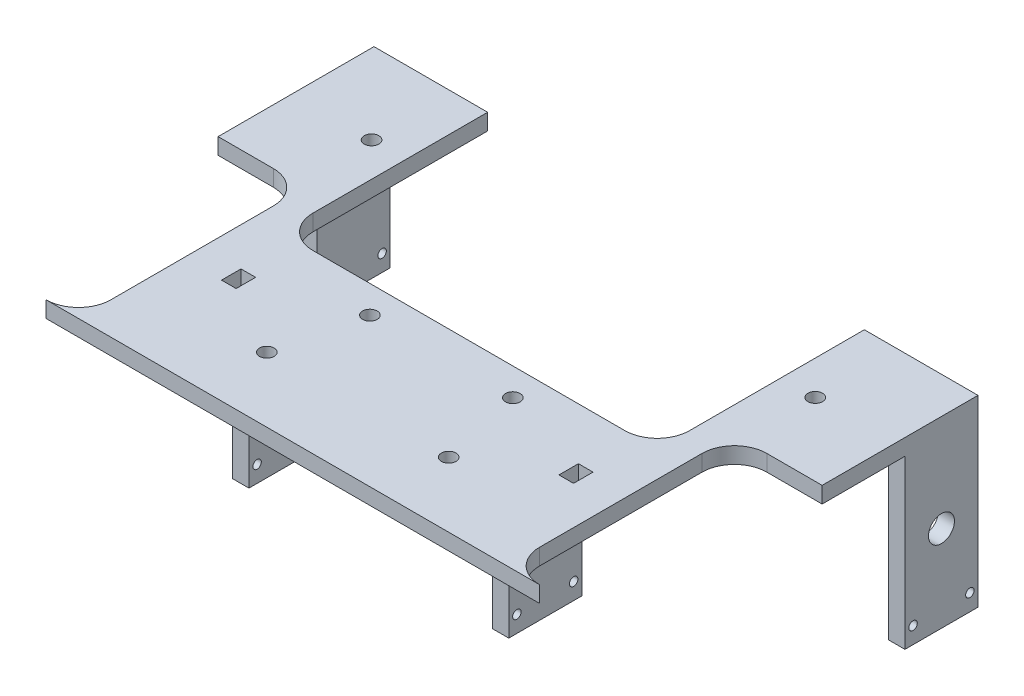
SolidWorks part; units mm, degrees
ref_plane "Front Plane" through (0, 0, 0) normal (0, 0, 1) x (1, 0, 0)
ref_plane "Top Plane" through (0, 0, 0) normal (0, 1, 0) x (1, 0, 0)
ref_plane "Right Plane" through (0, 0, 0) normal (1, 0, 0) x (0, 0, -1)
sketch "Sketch1" plane through (0, 0, 0) normal (0, 1, 0) x (1, 0, 0)
  line L0 (0, 0) -> (0, -300)
  line L1 (0, -300) -> (186, -300)
  line L2 (186, -300) -> (186, 0)
  line L3 (186, 0) -> (176, 0)
  line L4 (176, 0) -> (151, 0)
  line L5 (151, 0) -> (151, -56.1159)
  line L6 (151, -56.1159) -> (35, -56.1159)
  line L7 (35, -56.1159) -> (35, 0)
  line L8 (35, 0) -> (10, 0)
  line L9 (10, 0) -> (0, 0)
  line L10 (93, -300) -> (93, -56.1159) construction
  point P9 (93, -56.1159)
  dimension "D1" = 300
  dimension "D2" = 10
  dimension "D3" = 186
  dimension "D5" = 10
  dimension "D6" = 35
extrude "Boss-Extrude1" add sketch "Sketch1" along normal blind 5
sketch "Sketch2" plane through (0, 0, 0) normal (0, -1, 0) x (1, 0, 0)
  line L1 (50.5, 94) -> (55.5, 94)
  line L2 (50.5, 94) -> (50.5, 71.5)
  line L3 (50.5, 71.5) -> (55.5, 71.5)
  line L4 (55.5, 94) -> (55.5, 71.5)
  line L6 (135.5, 94) -> (130.5, 94)
  line L7 (135.5, 94) -> (135.5, 71.5)
  line L8 (135.5, 71.5) -> (130.5, 71.5)
  line L9 (130.5, 94) -> (130.5, 71.5)
  line L10 (0, 300) -> (186, 300) construction
  line L11 (186, 300) -> (186, 0) construction
  line L12 (0, 0) -> (0, 300) construction
  dimension "D1" = 5
  dimension "D2" = 22.5
  dimension "D3" = 5
  dimension "D4" = 206
  dimension "D5" = 22.5
  dimension "D6" = 50.5
  dimension "D7" = 50.5
extrude "Boss-Extrude2" add sketch "Sketch2" along normal blind 38
sketch "Sketch5" plane through (0, 0, 0) normal (0, -1, 0) x (1, 0, 0)
  line L0 (186, 300) -> (186, 0) construction
  line L1 (186, 295) -> (161, 295)
  line L2 (186, 295) -> (186, 300)
  line L3 (186, 300) -> (161, 300)
  line L4 (161, 295) -> (161, 300)
  line L5 (0, 300) -> (186, 300) construction
  line L6 (186, 240) -> (161, 240)
  line L7 (186, 240) -> (186, 245)
  line L8 (186, 245) -> (161, 245)
  line L9 (161, 240) -> (161, 245)
  line L10 (186, 185) -> (161, 185)
  line L11 (186, 185) -> (186, 190)
  line L12 (186, 190) -> (161, 190)
  line L13 (161, 185) -> (161, 190)
  line L14 (186, 130) -> (161, 130)
  line L15 (186, 130) -> (186, 135)
  line L16 (186, 135) -> (161, 135)
  line L17 (161, 130) -> (161, 135)
  dimension "D1" = 5
  dimension "D2" = 5
  dimension "D3" = 5
  dimension "D4" = 5
  dimension "D5" = 50
  dimension "D6" = 50
  dimension "D7" = 50
  dimension "D8" = 25
extrude "Boss-Extrude3" add sketch "Sketch5" along normal blind 30
fillet "Fillet3" radius 5 4 edges at (173.5, 0, 130) (173.5, 0, 185) (173.5, 0, 240) (173.5, 0, 295)
sketch "Sketch6" plane through (0, 0, 300) normal (0, 0, 1) x (1, 0, 0)
  line L0 (186, -30) -> (161, -30) construction
  line L1 (186, 5) -> (186, -30) construction
  circle A0 centre (178, -24) radius 3
  dimension "D1" = 6
  dimension "D2" = 6
  dimension "D3" = 8
extrude "Cut-Extrude4" cut sketch "Sketch6" against normal blind 172
sketch "Sketch7" plane through (0, 0, 0) normal (0, -1, 0) x (1, 0, 0)
  line L0 (0, 0) -> (0, 300) construction
  line L1 (0, 22.5) -> (5, 22.5)
  line L2 (0, 22.5) -> (0, 0)
  line L3 (0, 0) -> (5, 0)
  line L4 (5, 22.5) -> (5, 0)
  line L5 (186, 125) -> (186, 0) construction
  line L6 (186, 22.5) -> (181, 22.5)
  line L7 (186, 22.5) -> (186, 0)
  line L8 (186, 0) -> (181, 0)
  line L9 (181, 22.5) -> (181, 0)
  line L10 (186, 0) -> (151, 0) construction
  dimension "D1" = 5
  dimension "D2" = 5
  dimension "D3" = 22.5
  dimension "D4" = 22.5
extrude "Boss-Extrude4" add sketch "Sketch7" along normal blind 51.5
sketch "Sketch3" plane through (186, 0, 0) normal (1, 0, 0) x (0, 0, -1)
  line L4 (-71.5, 0) -> (-94, 0)
  line L5 (-71.5, -38) -> (-71.5, 0)
  line L6 (-94, -38) -> (-71.5, -38)
  line L7 (-94, 0) -> (-94, -38)
  line L9 (-71.5, -38) -> (-71.5, 0)
  line L10 (-94, -38) -> (-71.5, -38)
  line L11 (-94, 0) -> (-94, -38)
  line L13 (-71.5, 0) -> (-94, 0)
  circle A0 centre (-74, -32.9) radius 1.3 construction
  circle A1 centre (-91.5, -32.9) radius 1.3 construction
  circle A2 centre (-74, -32.9) radius 1.3
  circle A3 centre (-91.5, -32.9) radius 1.3
  circle A4 centre (-20, -46.4) radius 1.3 construction
  circle A5 centre (-2.5, -46.4) radius 1.3 construction
  circle A6 centre (-20, -46.4) radius 1.3
  circle A7 centre (-2.5, -46.4) radius 1.3
  dimension "D1" = 0
extrude "Cut-Extrude2" cut sketch "Sketch3" against normal through all contours A3 | A2 | A6 | A7
sketch "Sketch9" plane through (0, 0, 0) normal (0, -1, 0) x (1, 0, 0)
  line L0 (35, 0) -> (5, 0) construction
  line L1 (35, 0) -> (151, 0)
  line L2 (35, 0) -> (35, 63.7796)
  line L3 (35, 63.7796) -> (151, 63.7796)
  line L4 (151, 0) -> (151, 63.7796)
  line L5 (35, 56.1159) -> (35, 0) construction
  line L6 (151, 0) -> (151, 56.1159) construction
extrude "Cut-Extrude6" cut sketch "Sketch9" against normal blind 10
sketch "Sketch10" plane through (0, -30, 0) normal (0, -1, 0) x (1, 0, 0)
  line L1 (186, 295) -> (161, 295)
  line L2 (186, 295) -> (186, 300)
  line L3 (186, 300) -> (161, 300)
  line L4 (161, 295) -> (161, 300)
  line L5 (161, 130) -> (186, 130)
  line L6 (161, 130) -> (161, 135)
  line L7 (161, 135) -> (186, 135)
  line L8 (186, 130) -> (186, 135)
extrude "Boss-Extrude5" add sketch "Sketch10" along normal blind 70
sketch "Sketch11" plane through (186, 0, 0) normal (1, 0, 0) x (0, 0, -1)
  line L0 (-300, -100) -> (-304.9019, -134.6439)
  line L1 (-304.9019, -134.6439) -> (-300, -135.3374)
  line L2 (-300, -135.3374) -> (-295, -100)
  line L3 (-300, -100) -> (-295, -100)
extrude "Boss-Extrude6" add sketch "Sketch11" against normal blind 25
sketch "Sketch12" plane through (0, -100, 0) normal (0, -1, 0) x (1, 0, 0)
  line L1 (161, 130) -> (186, 130)
  line L2 (161, 130) -> (161, 135)
  line L3 (161, 135) -> (186, 135)
  line L4 (186, 130) -> (186, 135)
extrude "Boss-Extrude7" add sketch "Sketch12" along normal blind 19.72
sketch "Sketch13" plane through (0, 0, 130) normal (0, 0, -1) x (-1, 0, 0)
  line L0 (-186, -115.3141) -> (-186, -119.72)
  line L1 (-186, -119.72) -> (-186, -5) construction
  line L2 (-186, -119.72) -> (-161, -123.1352)
  line L3 (-161, -123.1352) -> (-161, -115.3141)
  line L4 (-161, -115.3141) -> (-186, -115.3141)
  line L5 (-161, -119.72) -> (-161, -5) construction
  line L8 (-88.5025, -135.5912) -> (-182.3051, -122.777) construction
extrude "Boss-Extrude8" add sketch "Sketch13" along normal blind 15 and the other way blind 4
sketch "Sketch14" plane through (19.4625, -142.4702, 0) normal (0.1354, -0.9908, 0) x (0.9908, 0.1354, 0)
  line L0 (186.3576, 115) -> (168.0843, 132.0374)
  line L1 (168.0843, 115) -> (142.8521, 115) construction
  line L2 (168.0843, 115) -> (168.0843, 134) construction
  line L3 (168.0843, 132.0374) -> (198.0152, 130.431)
  line L4 (198.0152, 130.431) -> (197.5151, 111.3666)
  line L5 (197.5151, 111.3666) -> (186.3576, 109.6075)
  line L6 (186.3576, 109.6075) -> (186.3576, 115)
extrude "Cut-Extrude7" cut sketch "Sketch14" against normal blind 15
sketch "Sketch15" plane through (0, 39.652, 280.2402) normal (0, 0.1401, 0.9901) x (1, 0, 0)
  line L1 (161, -141.043) -> (161, -176.032) construction
  line L2 (186, -141.043) -> (161, -141.043) construction
  line L3 (186, -141.043) -> (186, -176.032) construction
  line L4 (161, -176.032) -> (186, -176.032) construction
  circle A0 centre (178, -168.032) radius 2.25
  circle A1 centre (169, -149.043) radius 2.25
  dimension "D1" = 4.5
  dimension "D2" = 4.5
  dimension "D3" = 8
  dimension "D4" = 8
  dimension "D5" = 8
  dimension "D6" = 8
extrude "Cut-Extrude8" cut sketch "Sketch15" against normal blind 20
sketch "Sketch16" plane through (0, 0, 0) normal (0, -1, 0) x (1, 0, 0)
  line L1 (166, 272) -> (172, 272)
  line L2 (166, 272) -> (166, 275)
  line L3 (166, 275) -> (172, 275)
  line L4 (172, 272) -> (172, 275)
  line L5 (143.4, 272) -> (137.4, 272)
  line L6 (143.4, 272) -> (143.4, 275)
  line L7 (143.4, 275) -> (137.4, 275)
  line L8 (137.4, 272) -> (137.4, 275)
  line L9 (166, 217) -> (172, 217)
  line L10 (166, 217) -> (166, 220)
  line L11 (166, 220) -> (172, 220)
  line L12 (172, 217) -> (172, 220)
  line L13 (166, 162) -> (172, 162)
  line L14 (166, 162) -> (166, 165)
  line L15 (166, 165) -> (172, 165)
  line L16 (172, 162) -> (172, 165)
  line L17 (137.4, 217) -> (143.4, 217)
  line L18 (137.4, 217) -> (137.4, 220)
  line L19 (137.4, 220) -> (143.4, 220)
  line L20 (143.4, 217) -> (143.4, 220)
  line L21 (137.4, 162) -> (143.4, 162)
  line L22 (137.4, 162) -> (137.4, 165)
  line L23 (137.4, 165) -> (143.4, 165)
  line L24 (143.4, 162) -> (143.4, 165)
  line L25 (186, 180) -> (186, 135) construction
  line L28 (161, 295) -> (186, 295) construction
  line L29 (161, 240) -> (186, 240) construction
  line L30 (161, 185) -> (186, 185) construction
  dimension "D1" = 3
  dimension "D2" = 3
  dimension "D3" = 3
  dimension "D4" = 3
  dimension "D5" = 3
  dimension "D6" = 3
  dimension "D7" = 20
  dimension "D8" = 22.6
  dimension "D9" = 6
  dimension "D10" = 6
  dimension "D11" = 23
  dimension "D12" = 23
  dimension "D13" = 23
extrude "Boss-Extrude9" add sketch "Sketch16" along normal blind 12.4
sketch "Sketch17" plane through (0, 0, 162) normal (0, 0, -1) x (-1, 0, 0)
  arc A0 (-169.75, -6.8) -> (-169.75, -5.6) centre (-168.95, -6.2) ccw construction
  arc A1 (-169.75, -6.8) -> (-169.75, -5.6) centre (-168.95, -6.2) ccw
  circle A2 centre (-168.95, -6.2) radius 1
  circle A3 centre (-140.45, -6.2) radius 1
extrude "Cut-Extrude9" cut sketch "Sketch17" against normal through all contours A1 A2 | A3 region at (168.95, -6.2, 162)
sketch "Sketch27" plane through (19.4625, -142.4702, 0) normal (0.1354, -0.9908, 0) x (0.9908, 0.1354, 0)
  line L1 (142.8521, 115) -> (168.0843, 115)
  line L2 (142.8521, 115) -> (142.8521, 134)
  line L3 (142.8521, 134) -> (168.0843, 134)
  line L4 (168.0843, 115) -> (168.0843, 134)
extrude "Boss-Extrude11" add sketch "Sketch27" along normal blind 3
fillet "Fillet4" radius 5 6 edges at (140.4, 0, 275) (169, 0, 275) (140.4, 0, 220) (169, 0, 220) (140.4, 0, 165) (169, 0, 165)
sketch "Sketch18" plane through (0, -115.3141, 0) normal (0, 1, 0) x (1, 0, 0)
  circle A0 centre (174.8857, -120.9947) radius 2.25
  dimension "D1" = 4.5
extrude "Cut-Extrude10" cut sketch "Sketch18" against normal through all
sketch "Sketch19" plane through (0, 0, 0) normal (0, -1, 0) x (1, 0, 0)
  line L0 (42.3, 80.75) -> (39.8, 80.75) construction
  line L1 (39.8, 84.75) -> (39.8, 80.75) construction
  line L2 (42.3, 84.75) -> (42.3, 80.75) construction
  line L3 (39.8, 84.75) -> (42.3, 84.75) construction
  line L4 (42.3, 80.75) -> (39.8, 80.75) construction
  line L5 (39.8, 84.75) -> (39.8, 80.75) construction
  line L6 (42.3, 84.75) -> (42.3, 80.75) construction
  line L7 (39.8, 84.75) -> (42.3, 84.75) construction
  line L8 (143.7, 80.75) -> (143.7, 84.75) construction
  line L9 (143.7, 84.75) -> (146.2, 84.75) construction
  line L10 (146.2, 80.75) -> (146.2, 84.75) construction
  line L11 (146.2, 80.75) -> (143.7, 80.75) construction
  line L12 (143.7, 80.75) -> (143.7, 84.75) construction
  line L13 (143.7, 84.75) -> (146.2, 84.75) construction
  line L14 (146.2, 80.75) -> (146.2, 84.75) construction
  line L15 (146.2, 80.75) -> (143.7, 80.75) construction
  line L16 (43.3, 79.75) -> (38.8, 79.75)
  line L17 (38.8, 85.75) -> (38.8, 79.75)
  line L18 (38.8, 85.75) -> (43.3, 85.75)
  line L19 (43.3, 85.75) -> (43.3, 79.75)
  line L20 (142.7, 79.75) -> (142.7, 85.75)
  line L21 (142.7, 85.75) -> (147.2, 85.75)
  line L22 (147.2, 79.75) -> (147.2, 85.75)
  line L23 (147.2, 79.75) -> (142.7, 79.75)
  line L31 (151, 0) -> (181, 0)
  line L32 (181, 0) -> (181, 22.5)
  line L34 (186, 22.5) -> (186, 125)
  line L35 (186, 125) -> (161, 125)
  line L36 (161, 125) -> (161, 135)
  line L37 (161, 135) -> (186, 135)
  line L38 (186, 135) -> (186, 180)
  line L39 (186, 180) -> (161, 180)
  line L40 (161, 180) -> (161, 190)
  line L41 (161, 190) -> (186, 190)
  line L42 (186, 190) -> (186, 235)
  line L43 (186, 235) -> (161, 235)
  line L44 (161, 235) -> (161, 245)
  line L45 (161, 245) -> (186, 245)
  line L46 (186, 245) -> (186, 290)
  line L47 (186, 290) -> (161, 290)
  line L48 (161, 290) -> (161, 300)
  line L49 (161, 300) -> (0, 300)
  line L50 (0, 300) -> (0, 22.5)
  line L51 (0, 22.5) -> (5, 22.5)
  line L52 (5, 22.5) -> (5, 0)
  line L53 (5, 0) -> (35, 0)
  line L56 (151, 63.7796) -> (151, 0)
  line L57 (151, 63.7796) -> (151, 0)
  line L58 (35, 0) -> (35, 63.7796)
  line L61 (151, 0) -> (181, 0)
  line L64 (186, 22.5) -> (186, 125)
  line L65 (186, 125) -> (161, 125)
  line L66 (161, 125) -> (161, 135)
  line L67 (161, 135) -> (186, 135)
  line L68 (186, 135) -> (186, 180)
  line L69 (186, 180) -> (161, 180)
  line L70 (161, 180) -> (161, 190)
  line L71 (161, 190) -> (186, 190)
  line L72 (186, 190) -> (186, 235)
  line L73 (186, 235) -> (161, 235)
  line L74 (161, 235) -> (161, 245)
  line L75 (161, 245) -> (186, 245)
  line L76 (186, 245) -> (186, 290)
  line L77 (186, 290) -> (161, 290)
  line L78 (161, 290) -> (161, 300)
  line L79 (161, 300) -> (0, 300)
  line L80 (0, 300) -> (0, 22.5)
  line L81 (0, 22.5) -> (5, 22.5)
  line L82 (5, 22.5) -> (5, 0)
  line L83 (5, 0) -> (35, 0)
  line L106 (35, 0) -> (35, 63.7796)
  line L107 (35, 63.7796) -> (151, 63.7796)
  line L108 (35, 63.7796) -> (151, 63.7796)
  line L116 (181, 22.5) -> (186, 22.5)
  line L122 (181, 22.5) -> (186, 22.5)
  line L124 (181, 0) -> (181, 22.5)
  dimension "D1" = 0
  dimension "D2" = 1
  dimension "D3" = 1
extrude "Cut-Extrude12" cut sketch "Sketch19" against normal through all contours L23 L22 L21 L20 | L19 L18 L17 L16 region at (41.05, 0, 82.75) region at (144.95, 0, 82.75)
fillet "Fillet6" radius 10 2 edges at (151, 2.5, 63.7796) (35, 2.5, 63.7796)
sketch "Sketch21" plane through (0, 0, 0) normal (0, -1, 0) x (1, 0, 0)
  line L0 (0, 22.5) -> (0, 300) construction
  line L1 (0, 48) -> (27, 48)
  line L2 (0, 48) -> (0, 118)
  line L3 (0, 118) -> (27, 118)
  line L4 (27, 48) -> (27, 118)
  line L5 (186, 125) -> (186, 22.5) construction
  line L6 (186, 48) -> (159, 48)
  line L7 (186, 48) -> (186, 118)
  line L8 (186, 118) -> (159, 118)
  line L9 (159, 48) -> (159, 118)
  line L10 (0, 300) -> (161, 300) construction
  dimension "D1" = 70
  dimension "D2" = 182
  dimension "D3" = 70
  dimension "D4" = 182
  dimension "D5" = 27
  dimension "D6" = 27
extrude "Cut-Extrude14" cut sketch "Sketch21" against normal through all
fillet "Fillet7" radius 10 4 edges at (27, 2.5, 118) (27, 2.5, 48) (159, 2.5, 48) (159, 2.5, 118)
sketch "Sketch22" plane through (0, 0, 0) normal (0, -1, 0) x (1, 0, 0)
  line L34 (17, 48) -> (0, 48)
  line L35 (0, 48) -> (0, 22.5)
  line L36 (0, 22.5) -> (5, 22.5)
  line L37 (5, 22.5) -> (5, 0)
  line L38 (5, 0) -> (35, 0)
  line L39 (35, 0) -> (35, 53.7796)
  line L40 (45, 63.7796) -> (141, 63.7796)
  line L41 (151, 53.7796) -> (151, 0)
  line L42 (151, 0) -> (181, 0)
  line L43 (181, 0) -> (181, 22.5)
  line L44 (181, 22.5) -> (186, 22.5)
  line L45 (186, 22.5) -> (186, 48)
  line L46 (186, 48) -> (169, 48)
  line L47 (159, 58) -> (159, 108)
  line L48 (169, 118) -> (186, 118)
  line L49 (186, 118) -> (186, 125)
  line L50 (186, 125) -> (161, 125)
  line L51 (161, 125) -> (161, 135)
  line L52 (161, 135) -> (186, 135)
  line L53 (186, 135) -> (186, 180)
  line L54 (186, 180) -> (161, 180)
  line L55 (161, 180) -> (161, 190)
  line L56 (161, 190) -> (186, 190)
  line L57 (186, 190) -> (186, 235)
  line L58 (186, 235) -> (161, 235)
  line L59 (161, 235) -> (161, 245)
  line L60 (161, 245) -> (186, 245)
  line L61 (186, 245) -> (186, 290)
  line L62 (186, 290) -> (161, 290)
  line L63 (161, 290) -> (161, 300)
  line L64 (161, 300) -> (0, 300)
  line L65 (0, 300) -> (0, 118)
  line L66 (0, 118) -> (17, 118)
  line L67 (27, 108) -> (27, 58)
  line L68 (17, 48) -> (0, 48)
  line L69 (0, 48) -> (0, 22.5)
  line L70 (0, 22.5) -> (5, 22.5)
  line L71 (5, 22.5) -> (5, 0)
  line L72 (5, 0) -> (35, 0)
  line L73 (35, 0) -> (35, 53.7796)
  line L74 (45, 63.7796) -> (141, 63.7796)
  line L75 (151, 53.7796) -> (151, 0)
  line L76 (151, 0) -> (181, 0)
  line L77 (181, 0) -> (181, 22.5)
  line L78 (181, 22.5) -> (186, 22.5)
  line L79 (186, 22.5) -> (186, 48)
  line L80 (186, 48) -> (169, 48)
  line L81 (159, 58) -> (159, 108)
  line L82 (169, 118) -> (186, 118)
  line L83 (186, 118) -> (186, 125)
  line L84 (186, 125) -> (161, 125)
  line L85 (161, 125) -> (161, 135)
  line L86 (161, 135) -> (186, 135)
  line L87 (186, 135) -> (186, 180)
  line L88 (186, 180) -> (161, 180)
  line L89 (161, 180) -> (161, 190)
  line L90 (161, 190) -> (186, 190)
  line L91 (186, 190) -> (186, 235)
  line L92 (186, 235) -> (161, 235)
  line L93 (161, 235) -> (161, 245)
  line L94 (161, 245) -> (186, 245)
  line L95 (186, 245) -> (186, 290)
  line L96 (186, 290) -> (161, 290)
  line L97 (161, 290) -> (161, 300)
  line L98 (161, 300) -> (0, 300)
  line L99 (0, 300) -> (0, 118)
  line L100 (0, 118) -> (17, 118)
  line L101 (27, 108) -> (27, 58)
  circle A4 centre (24.5, 25.25) radius 2.25 construction
  circle A5 centre (24.5, 25.25) radius 2.25
  arc A6 (45, 63.7796) -> (35, 53.7796) centre (45, 53.7796) ccw
  arc A7 (151, 53.7796) -> (141, 63.7796) centre (141, 53.7796) ccw
  arc A8 (159, 58) -> (169, 48) centre (169, 58) ccw
  arc A9 (169, 118) -> (159, 108) centre (169, 108) ccw
  arc A10 (27, 108) -> (17, 118) centre (17, 108) ccw
  arc A11 (17, 48) -> (27, 58) centre (17, 58) ccw
  arc A12 (45, 63.7796) -> (35, 53.7796) centre (45, 53.7796) ccw
  arc A13 (151, 53.7796) -> (141, 63.7796) centre (141, 53.7796) ccw
  arc A14 (159, 58) -> (169, 48) centre (169, 58) ccw
  arc A15 (169, 118) -> (159, 108) centre (169, 108) ccw
  arc A16 (27, 108) -> (17, 118) centre (17, 108) ccw
  arc A17 (17, 48) -> (27, 58) centre (17, 58) ccw
  circle A18 centre (161.5, 25.6175) radius 2.25 construction
  circle A19 centre (161.5, 25.6175) radius 2.25
  circle A20 centre (115, 72.25) radius 2.25 construction
  circle A21 centre (115, 72.25) radius 2.25
  circle A22 centre (71, 72.25) radius 2.25 construction
  circle A23 centre (71, 72.25) radius 2.25
  point P19 (0, 0)
  point P35 (0, 0)
  point P37 (63, 76.0448)
  point P40 (0, 0)
  dimension "D1" = 0
extrude "Cut-Extrude16" cut sketch "Sketch22" against normal blind 10 contours A5 | A19 | A23 | A21
sketch "Sketch23" plane through (0, 0, 135) normal (0, 0, 1) x (1, 0, 0)
  line L1 (178.1063, -118.4368) -> (161.0628, -118.4368)
  line L2 (178.1063, -118.4368) -> (178.1063, -123.5756)
  line L3 (178.1063, -123.5756) -> (161.0628, -123.5756)
  line L4 (161.0628, -118.4368) -> (161.0628, -123.5756)
extrude "Boss-Extrude10" add sketch "Sketch23" along normal blind 7
sketch "Sketch24" plane through (161.0628, 0, 0) normal (-1, 0, 0) x (0, 0, 1)
  line L0 (295, -100) -> (133.6076, -122.8359) construction
  line L1 (142, -121.6484) -> (135, -122.6389)
  line L2 (135, -119.72) -> (135, -123.5756) construction
  line L3 (142, -118.4368) -> (142, -123.5756) construction
  line L4 (142, -121.6484) -> (142, -124.3381)
  line L5 (142, -124.3381) -> (134.715, -124.3381)
  line L6 (134.715, -124.3381) -> (135, -122.6389)
extrude "Cut-Extrude17" cut sketch "Sketch24" against normal up to next
sketch "Sketch25" plane through (0, -118.4368, 0) normal (0, 1, 0) x (1, 0, 0)
  circle A0 centre (174.7191, -138.0894) radius 2.25
  dimension "D1" = 4.5
extrude "Cut-Extrude18" cut sketch "Sketch25" against normal up to next
sketch "Sketch28" plane through (0, 5, 0) normal (0, 1, 0) x (1, 0, 0)
  line L0 (0, -300) -> (186, -300) construction
  circle A0 centre (93, -260) radius 2.25
  point P4 (93, -300)
  dimension "D1" = 4.5
  dimension "D2" = 40
extrude "Cut-Extrude19" cut sketch "Sketch28" against normal through all
sketch "Sketch30" plane through (0, 5, 0) normal (0, 1, 0) x (1, 0, 0)
  line L0 (186, -118) -> (169, -118) construction
  line L1 (-59.5189, -331.927) -> (379.4222, -331.927)
  line L2 (-59.5189, -331.927) -> (-59.5189, -118)
  line L3 (-59.5189, -118) -> (379.4222, -118)
  line L4 (379.4222, -331.927) -> (379.4222, -118)
extrude "Cut-Extrude22" cut sketch "Sketch30" against normal through all
sketch "Sketch31" plane through (0, 0, 115) normal (0, 0, -1) x (-1, 0, 0)
  line L1 (-129.7503, -141.3628) -> (-212.8844, -141.3628)
  line L2 (-129.7503, -141.3628) -> (-129.7503, -112.7031)
  line L3 (-129.7503, -112.7031) -> (-212.8844, -112.7031)
  line L4 (-212.8844, -141.3628) -> (-212.8844, -112.7031)
extrude "Cut-Extrude23" cut sketch "Sketch31" against normal through all
sketch "Sketch32" plane through (0, 0, 0) normal (0, -1, 0) x (1, 0, 0)
  line L0 (169, 118) -> (17, 118) construction
  line L1 (186, 48) -> (186, 22.5) construction
  line L2 (0, 22.5) -> (0, 48) construction
  circle A0 centre (121, 98) radius 2.25
  circle A1 centre (65, 98) radius 2.25
  dimension "D1" = 4.5
  dimension "D2" = 4.5
  dimension "D3" = 20
  dimension "D4" = 20
  dimension "D5" = 65
  dimension "D6" = 65
extrude "Cut-Extrude24" cut sketch "Sketch32" against normal through all
sketch "Sketch33" plane through (55.5, 0, 0) normal (1, 0, 0) x (0, 0, -1)
  line L4 (-71.5, -38) -> (-71.5, 0)
  line L5 (-71.5, 0) -> (-94, 0)
  line L6 (-94, 0) -> (-94, -38)
  line L7 (-94, -38) -> (-71.5, -38)
  line L8 (-71.5, -38) -> (-71.5, 0)
  line L10 (-94, 0) -> (-94, -38)
  line L11 (-94, -38) -> (-71.5, -38)
  line L12 (-71.5, 0) -> (-94, 0)
  circle A0 centre (-82.75, -11.4) radius 2.675 construction
  circle A1 centre (-82.75, -11.4) radius 2.675 construction
  circle A2 centre (-82.75, -11.4) radius 4
  dimension "D2" = 8
  dimension "D1" = 0
extrude "Cut-Extrude26" cut sketch "Sketch33" against normal blind 10 and the other way blind 110 contours A2
sketch "Sketch34" plane through (186, 0, 0) normal (1, 0, 0) x (0, 0, -1)
  line L6 (0, 5) -> (-48, 5)
  line L7 (-48, 5) -> (-48, 0)
  line L8 (-48, 0) -> (-22.5, 0)
  line L9 (-22.5, 0) -> (-22.5, -51.5)
  line L10 (-22.5, -51.5) -> (0, -51.5)
  line L11 (0, -51.5) -> (0, 5)
  line L12 (0, 5) -> (-48, 5)
  line L13 (-48, 5) -> (-48, 0)
  line L14 (-48, 0) -> (-22.5, 0)
  line L15 (-22.5, 0) -> (-22.5, -51.5)
  line L16 (-22.5, -51.5) -> (0, -51.5)
  line L17 (0, -51.5) -> (0, 5)
  circle A0 centre (-11.25, -24.9) radius 2.675 construction
  circle A1 centre (-11.25, -24.9) radius 2.675 construction
  circle A2 centre (-11.25, -24.9) radius 4
  dimension "D2" = 8
  dimension "D1" = 0
extrude "Cut-Extrude27" cut sketch "Sketch34" against normal through all contours A2
